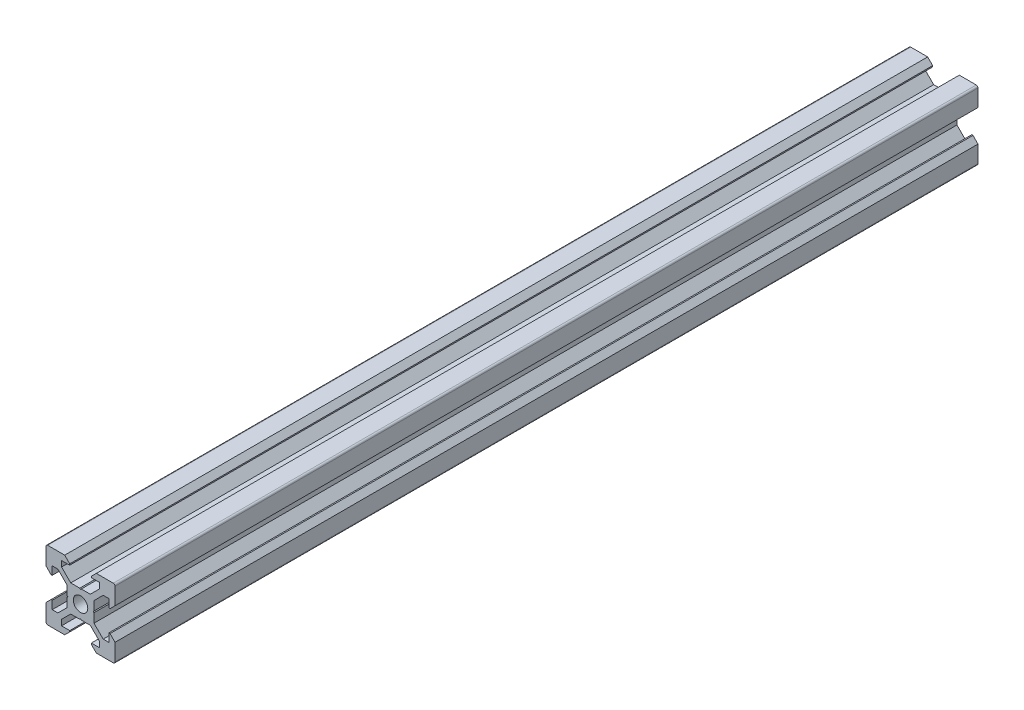
SolidWorks part; units mm, degrees
material "6061-T6 (SS)"
ref_plane "Front Plane" through (0, 0, 0) normal (0, 0, 1) x (1, 0, 0)
ref_plane "Top Plane" through (0, 0, 0) normal (0, 1, 0) x (1, 0, 0)
ref_plane "Right Plane" through (0, 0, 0) normal (1, 0, 0) x (0, 0, -1)
sketch "Sketch1" plane through (0, 0, 0) normal (0, 0, 1) x (1, 0, 0)
  line L1 (9.5, -10) -> (-9.5, -10)
  line L2 (10, -9.5) -> (10, 9.5)
  line L3 (9.5, 10) -> (-9.5, 10)
  line L4 (-10, -9.5) -> (-10, 9.5)
  line L5 (10, -10) -> (-10, 10) construction
  line L6 (10, 10) -> (-10, -10) construction
  circle A0 centre (0, 0) radius 2.1
  arc A1 (-9.5, 10) -> (-10, 9.5) centre (-9.5, 9.5) ccw
  arc A2 (10, 9.5) -> (9.5, 10) centre (9.5, 9.5) ccw
  arc A3 (9.5, -10) -> (10, -9.5) centre (9.5, -9.5) ccw
  arc A4 (-9.5, -10) -> (-10, -9.5) centre (-9.5, -9.5) cw
  point P0 (0, 0)
  line B0 (0, 0) -> (0, 10) construction
  line B1 (0, 3.69) -> (-0.21, 3.9)
  line B2 (-0.21, 3.9) -> (-2.8393, 3.9)
  line B3 (-2.8393, 3.9) -> (-5.5, 6.5607)
  line B4 (-5.5, 6.5607) -> (-5.5, 8.2)
  line B5 (-5.5, 8.2) -> (-3.125, 8.2)
  line B6 (-3.125, 8.2) -> (-3.125, 8.545)
  line B7 (-3.125, 8.545) -> (-4.58, 10)
  line B8 (-4.58, 10) -> (4.58, 10)
  line B9 (0, 0) -> (-5.9132, 5.9132) construction
  line B10 (3.125, 8.545) -> (4.58, 10)
  line B11 (3.125, 8.2) -> (3.125, 8.545)
  line B12 (5.5, 8.2) -> (3.125, 8.2)
  line B13 (5.5, 6.5607) -> (5.5, 8.2)
  line B14 (2.8393, 3.9) -> (5.5, 6.5607)
  line B15 (0.21, 3.9) -> (2.8393, 3.9)
  line B16 (0, 3.69) -> (0.21, 3.9)
  line B17 (0, 0) -> (-10, 0) construction
  line B18 (-3.69, 0) -> (-3.9, -0.21)
  line B19 (-3.9, -0.21) -> (-3.9, -2.8393)
  line B20 (-3.9, -2.8393) -> (-6.5607, -5.5)
  line B21 (-6.5607, -5.5) -> (-8.2, -5.5)
  line B22 (-8.2, -5.5) -> (-8.2, -3.125)
  line B23 (-8.2, -3.125) -> (-8.545, -3.125)
  line B24 (-8.545, -3.125) -> (-10, -4.58)
  line B25 (-10, -4.58) -> (-10, 4.58)
  line B26 (0, 0) -> (-5.9132, -5.9132) construction
  line B27 (-8.545, 3.125) -> (-10, 4.58)
  line B28 (-8.2, 3.125) -> (-8.545, 3.125)
  line B29 (-8.2, 5.5) -> (-8.2, 3.125)
  line B30 (-6.5607, 5.5) -> (-8.2, 5.5)
  line B31 (-3.9, 2.8393) -> (-6.5607, 5.5)
  line B32 (-3.9, 0.21) -> (-3.9, 2.8393)
  line B33 (-3.69, 0) -> (-3.9, 0.21)
  line B34 (0, 0) -> (0, -10) construction
  line B35 (0, -3.69) -> (0.21, -3.9)
  line B36 (0.21, -3.9) -> (2.8393, -3.9)
  line B37 (2.8393, -3.9) -> (5.5, -6.5607)
  line B38 (5.5, -6.5607) -> (5.5, -8.2)
  line B39 (5.5, -8.2) -> (3.125, -8.2)
  line B40 (3.125, -8.2) -> (3.125, -8.545)
  line B41 (3.125, -8.545) -> (4.58, -10)
  line B42 (4.58, -10) -> (-4.58, -10)
  line B43 (0, 0) -> (5.9132, -5.9132) construction
  line B44 (-3.125, -8.545) -> (-4.58, -10)
  line B45 (-3.125, -8.2) -> (-3.125, -8.545)
  line B46 (-5.5, -8.2) -> (-3.125, -8.2)
  line B47 (-5.5, -6.5607) -> (-5.5, -8.2)
  line B48 (-2.8393, -3.9) -> (-5.5, -6.5607)
  line B49 (-0.21, -3.9) -> (-2.8393, -3.9)
  line B50 (0, -3.69) -> (-0.21, -3.9)
  line B51 (0, 0) -> (10, 0) construction
  line B52 (3.69, 0) -> (3.9, 0.21)
  line B53 (3.9, 0.21) -> (3.9, 2.8393)
  line B54 (3.9, 2.8393) -> (6.5607, 5.5)
  line B55 (6.5607, 5.5) -> (8.2, 5.5)
  line B56 (8.2, 5.5) -> (8.2, 3.125)
  line B57 (8.2, 3.125) -> (8.545, 3.125)
  line B58 (8.545, 3.125) -> (10, 4.58)
  line B59 (10, 4.58) -> (10, -4.58)
  line B60 (0, 0) -> (5.9132, 5.9132) construction
  line B61 (8.545, -3.125) -> (10, -4.58)
  line B62 (8.2, -3.125) -> (8.545, -3.125)
  line B63 (8.2, -5.5) -> (8.2, -3.125)
  line B64 (6.5607, -5.5) -> (8.2, -5.5)
  line B65 (3.9, -2.8393) -> (6.5607, -5.5)
  line B66 (3.9, -0.21) -> (3.9, -2.8393)
  line B67 (3.69, 0) -> (3.9, -0.21)
  dimension "D1" = 4.2
  dimension "D3" = 0.5
  dimension "D2" = 20
sketch_block_instance "V Slot 1-4"
sketch_block "V Slot 1" parameters "D1"=10, "D2"=11, "D3"=4.3, "D4"=1.8, "D5"=0.21, "D6"=45, "D7"=9.16, "D8"=1.5, "D9"=6.25
sketch_block_instance "V Slot 1-5"
sketch_block_instance "V Slot 1-6"
sketch_block_instance "V Slot 1-7"
extrude "Boss-Extrude1" add sketch "Sketch1" along normal blind 250 contours B67 B52 B53 B54 B55 B56 B57 B58 L2 A2 L3 B10 B11 B12 B13 B14 B15 B16 B1 B2 B3 B4 B5 B6 B7 A1 L4 B27 B28 B29 B30 B31 B32 B33 B18 B19 B20 B21 B22 B23 B24 A4 L1 B44 B45 B46 B47 B48 B49 region at (7.04, -9.7172, 0)
